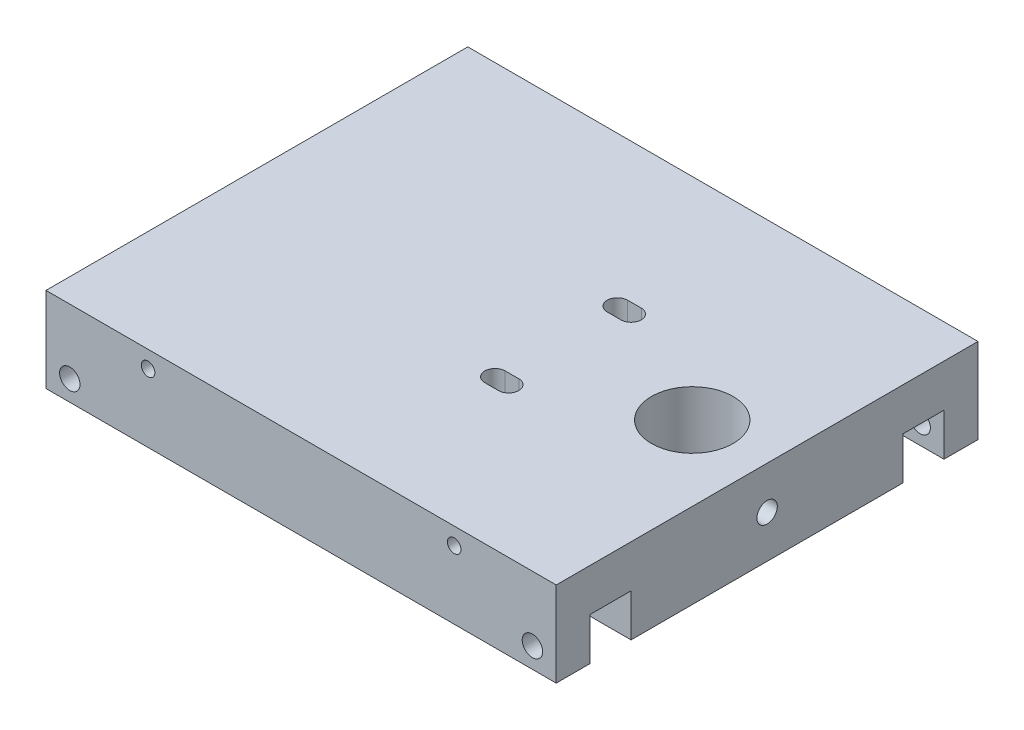
SolidWorks part; units mm, degrees
ref_plane "Front Plane" through (0, 0, 0) normal (0, 0, 1) x (1, 0, 0)
ref_plane "Top Plane" through (0, 0, 0) normal (0, 1, 0) x (1, 0, 0)
ref_plane "Right Plane" through (0, 0, 0) normal (1, 0, 0) x (0, 0, -1)
sketch "Sketch1" plane through (0, 0, 0) normal (0, 1, 0) x (1, 0, 0)
  line L0 (-75, 52) -> (75, 52)
  line L1 (-75, 62) -> (75, 62)
  line L2 (-75, 62) -> (-75, -62)
  line L3 (-75, -62) -> (75, -62)
  line L4 (75, 62) -> (75, -62)
  line L5 (0, -62) -> (0, 62) construction
  line L6 (-75, 0) -> (75, 0) construction
  line L7 (-75, 40) -> (75, 40)
  line L8 (-75, 40) -> (-75, -40)
  line L9 (-75, -40) -> (75, -40)
  line L10 (75, 40) -> (75, -40)
  line L11 (0, -40) -> (0, 40) construction
  line L12 (-75, 0) -> (75, 0) construction
  line L13 (-75, -52) -> (75, -52)
  circle A0 centre (53, 0) radius 12
  point P0 (0, 0)
  point P4 (0, 0)
  dimension "D7" = 24
  dimension "D1" = 124
  dimension "D2" = 150
  dimension "D3" = 80
  dimension "D4" = 150
  dimension "D5" = 12
  dimension "D6" = 12
  dimension "D8" = 22
  dimension "D9" = 150
extrude "Boss-Extrude1" add sketch "Sketch1" along normal blind 12.5 contours L2 L9 L4 L7 | L13 L2 L3 L4 | L4 L1 L2 L0 region at (0, 0, -57) region at (-2.0763, 0, 0) region at (0, 0, 57)
extrude "Boss-Extrude2" add sketch "Sketch1<3>" along normal blind 12.5 from surface contours L13 L2 L3 L4 | L2 L13 L4 L9 | L2 L7 L4 L0 | L4 L1 L2 L0 | L2 L9 L4 L7 region at (0, 0, -57) region at (0, 0, -46) region at (-2.0763, 0, 0) region at (0, 0, 46) region at (0, 0, 57) starting at face at (53, 12.5, 12)
sketch "Sketch1<3>" plane through (0, 0, 0) normal (0, 1, 0) x (1, 0, 0) same geometry as "Sketch1"
sketch "Sketch2" plane through (0, 0, 0) normal (0, -1, 0) x (1, 0, 0)
  line L0 (97.0851, 0) -> (-97.0851, 0) construction
  line L1 (13, 21) -> (17, 21)
  line L2 (13, 15) -> (17, 15)
  line L3 (-75, 62) -> (75, 62) construction
  line L4 (75, -40) -> (75, 40) construction
  line L5 (13, -15) -> (17, -15)
  line L6 (13, -21) -> (17, -21)
  line L7 (13, 25) -> (17, 25)
  line L8 (13, 11) -> (17, 11)
  line L9 (13, -11) -> (17, -11)
  line L10 (13, -25) -> (17, -25)
  circle A0 centre (13, 18) radius 3
  circle A1 centre (17, 18) radius 3
  circle A2 centre (17, -18) radius 3
  circle A3 centre (13, -18) radius 3
  arc A4 (17, 11) -> (17, 25) centre (17, 18) ccw
  arc A5 (13, 25) -> (13, 11) centre (13, 18) ccw
  arc A6 (17, -11) -> (17, -25) centre (17, -18) cw
  arc A7 (13, -25) -> (13, -11) centre (13, -18) cw
  point P4 (0, 0)
  dimension "D1" = 6
  dimension "D2" = 6
  dimension "D5" = 58
  dimension "D6" = 14
  dimension "D7" = 14
  dimension "D3" = 4
  dimension "D4" = 41
extrude "Cut-Extrude1" cut sketch "Sketch2" against normal through all contours A3 A2 | L5 A3 A2 | A3 A2 | A2 A3 L6 | A2 A3 | A1 A0 | A1 L1 A0 | A0 A1 | A1 A0 | A1 A0 L2 region at (12.4388, 0, 18) region at (15, 0, 20.7769) region at (17.5612, 0, 18) region at (15, 0, 15.2231) region at (15, 0, 18) region at (12.4388, 0, -18) region at (15, 0, -15.2231) region at (17.5612, 0, -18) region at (15, 0, -20.7769) region at (15, 0, -18)
extrude "Cut-Extrude2" cut sketch "Sketch2<3>" against normal blind 10 contours L7 A5 L8 A4 A1 L2 A0 L1 | A7 L10 A6 L9 L6 A3 L5 A2 region at (15, 0, 24.772) region at (15, 0, -11.228)
sketch "Sketch2<3>" plane through (0, 0, 0) normal (0, -1, 0) x (1, 0, 0) same geometry as "Sketch2"
sketch "Sketch3" plane through (75, 0, 0) normal (1, 0, 0) x (0, 0, -1)
  line L0 (40, 0) -> (-40, 0) construction
  circle A0 centre (0, 12.5) radius 3
  dimension "D1" = 6
  dimension "D2" = 12.5
extrude "Cut-Extrude3" cut sketch "Sketch3" against normal blind 15
sketch "Sketch4" plane through (0, 0, 62) normal (0, 0, 1) x (1, 0, 0)
  line L0 (75, 25) -> (-75, 25) construction
  line L1 (-45, 20) -> (45, 20) construction
  line L3 (-75, 0) -> (75, 0) construction
  line L4 (-75, 25) -> (-75, 0) construction
  line L5 (0, -55) -> (0, 55) construction
  circle A0 centre (-45, 20) radius 2
  circle A1 centre (45, 20) radius 2
  circle A2 centre (-68, 6) radius 3
  circle A3 centre (68, 6) radius 3
  point P6 (0, 20)
  dimension "D1" = 4
  dimension "D2" = 4
  dimension "D5" = 6
  dimension "D3" = 90
  dimension "D4" = 5
  dimension "D6" = 6
  dimension "D7" = 7
extrude "Cut-Extrude4" cut sketch "Sketch4" against normal blind 18
extrude "Cut-Extrude5" cut sketch "Sketch4<2>" along normal blind 18 from surface starting at face at (0, 12.5, -62)
sketch "Sketch4<2>" plane through (0, 0, 62) normal (0, 0, 1) x (1, 0, 0) same geometry as "Sketch4"
sketch "Sketch5" plane through (0, 25, 0) normal (0, 1, 0) x (1, 0, 0)
  line L0 (13, -15) -> (17, -15) construction
  line L1 (13, -21) -> (17, -21) construction
  line L2 (13, 21) -> (17, 21) construction
  line L3 (13, 15) -> (17, 15) construction
  line L4 (-75, 62) -> (-75, -62)
  line L5 (-75, -62) -> (75, -62)
  line L6 (75, -62) -> (75, 62)
  line L7 (75, 62) -> (-75, 62)
  line L8 (-75, 62) -> (-75, -62)
  line L9 (-75, -62) -> (75, -62)
  line L10 (75, -62) -> (75, 62)
  line L11 (75, 62) -> (-75, 62)
  line L12 (13, -15) -> (17, -15)
  line L13 (13, -21) -> (17, -21)
  line L14 (13, 21) -> (17, 21)
  line L15 (13, 15) -> (17, 15)
  circle A0 centre (53, 0) radius 12 construction
  arc A1 (13, -15) -> (13, -21) centre (13, -18) ccw construction
  arc A2 (17, -21) -> (17, -15) centre (17, -18) ccw construction
  arc A3 (13, 21) -> (13, 15) centre (13, 18) ccw construction
  arc A4 (17, 15) -> (17, 21) centre (17, 18) ccw construction
  circle A5 centre (53, 0) radius 12
  arc A6 (13, -15) -> (13, -21) centre (13, -18) ccw
  arc A7 (17, -21) -> (17, -15) centre (17, -18) ccw
  arc A8 (13, 21) -> (13, 15) centre (13, 18) ccw
  arc A9 (17, 15) -> (17, 21) centre (17, 18) ccw
  dimension "D2" = 40
  dimension "D3" = 36
  dimension "D4" = 18
  dimension "D5" = 22
  dimension "D1" = 0
